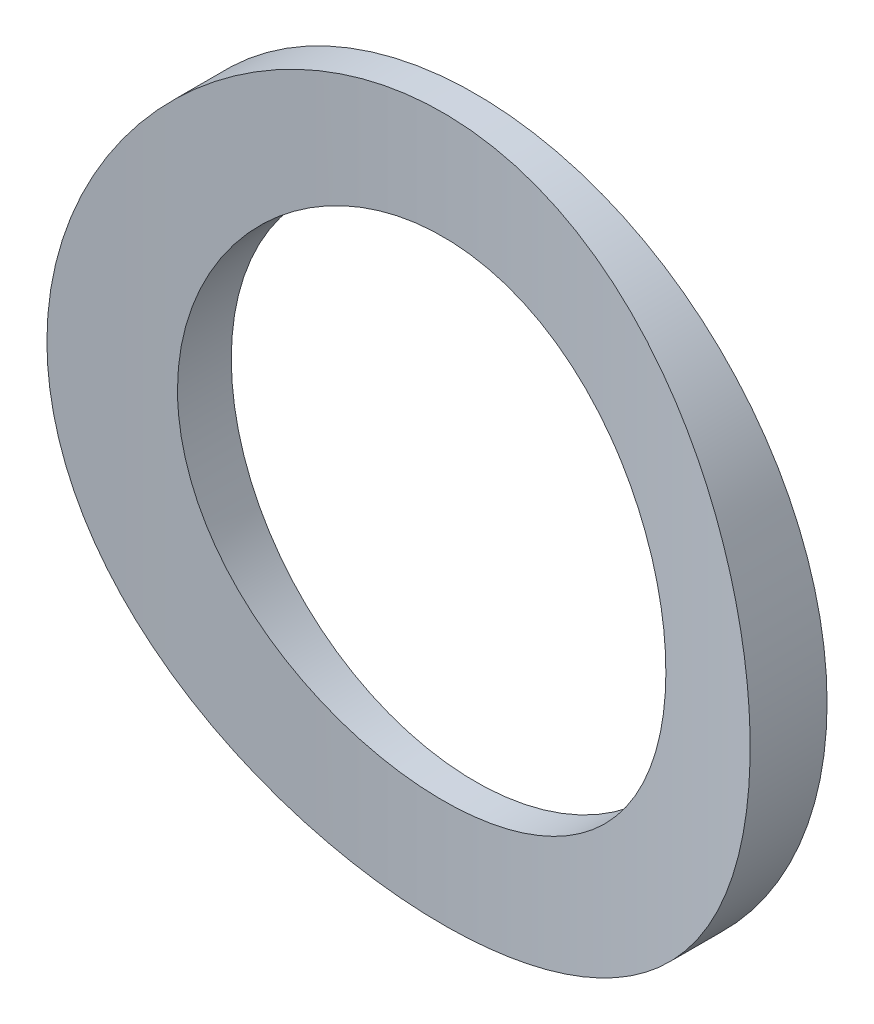
SolidWorks part; units mm, degrees
material "PTFE (general)"
ref_plane "Front Plane" through (0, 0, 0) normal (0, 0, 1) x (1, 0, 0)
ref_plane "Top Plane" through (0, 0, 0) normal (0, 1, 0) x (1, 0, 0)
ref_plane "Right Plane" through (0, 0, 0) normal (1, 0, 0) x (0, 0, -1)
sketch "Sketch1" plane through (0, 0, 0) normal (0, 0, 1) x (1, 0, 0)
  circle A0 centre (0, 0) radius 10.8
  circle A1 centre (0, 0) radius 7.5
  dimension "D1" = 21.6
  dimension "D2" = 15
extrude "Boss-Extrude1" add sketch "Sketch1" along normal blind 30
sketch "Sketch2" plane through (0, 0, 0) normal (0, 1, 0) x (1, 0, 0)
  line L0 (10.8, 0) -> (-10.8, 0) construction
  circle A0 centre (0, -44.5) radius 43.5
  dimension "D1" = 87
  dimension "D2" = 44.5
extrude "Cut-Extrude1" cut sketch "Sketch2" against normal through all both and the other way through all
